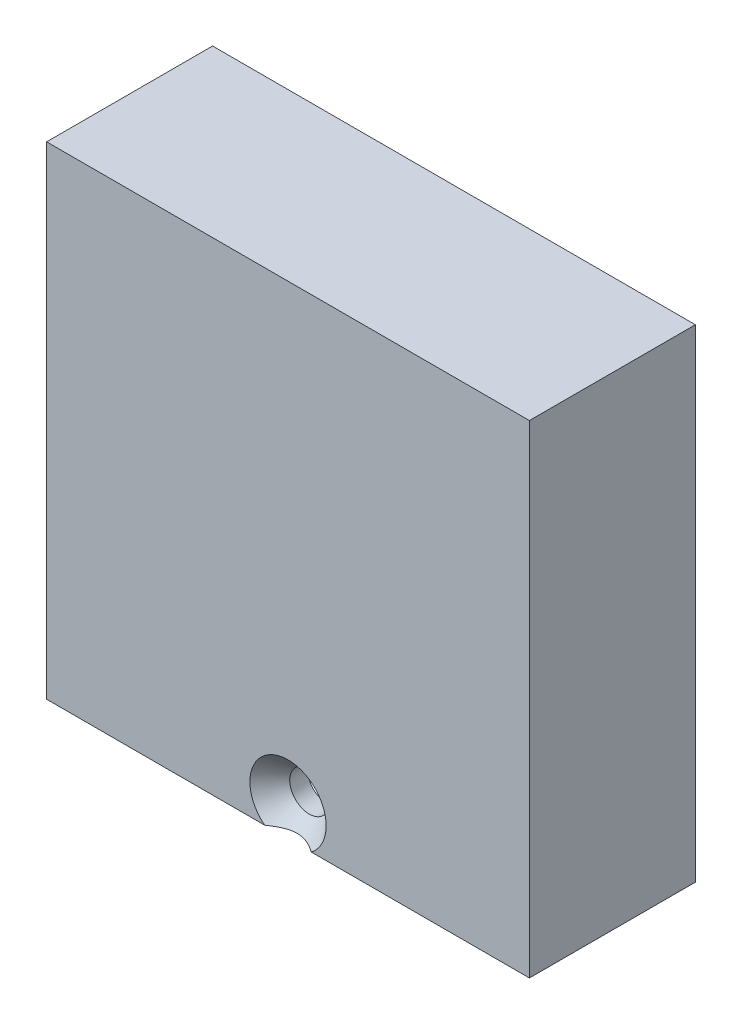
SolidWorks part; units mm, degrees
ref_plane "Plan de face" through (0, 0, 0) normal (0, 0, 1) x (1, 0, 0)
ref_plane "Plan de dessus" through (0, 0, 0) normal (0, 1, 0) x (1, 0, 0)
ref_plane "Plan de droite" through (0, 0, 0) normal (1, 0, 0) x (0, 0, -1)
sketch "Esquisse1" plane through (0, 0, 0) normal (0, 0, 1) x (1, 0, 0)
  line L1 (0, 0) -> (32, 0)
  line L2 (0, 0) -> (0, 32)
  line L3 (0, 32) -> (32, 32)
  line L4 (32, 0) -> (32, 32)
  dimension "D1" = 32
  dimension "D2" = 32
extrude "Main" add sketch "Esquisse1" along normal blind 11
sketch "Esquisse2" plane through (0, 0, 0) normal (0, -1, 0) x (1, 0, 0)
  line L0 (3.75, 0) -> (3.75, 5.2)
  line L1 (0, 0) -> (32, 0) construction
  line L2 (3.75, 5.2) -> (4.35, 5.2)
  line L3 (4.35, 5.2) -> (4.35, 6.2)
  line L4 (4.35, 6.2) -> (3.75, 6.2)
  line L5 (3.75, 6.2) -> (3.75, 8.4)
  line L6 (3.75, 8.4) -> (28.25, 8.4)
  line L7 (28.25, 8.4) -> (28.25, 6.2)
  line L8 (28.25, 6.2) -> (27.65, 6.2)
  line L9 (27.65, 6.2) -> (27.65, 5.2)
  line L10 (27.65, 5.2) -> (28.25, 5.2)
  line L11 (28.25, 5.2) -> (28.25, 0)
  line L12 (28.25, 0) -> (3.75, 0)
  line L13 (0, 11) -> (32, 11) construction
  point P13 (16, 0)
  point P15 (16, 8)
  point P18 (16, 11)
  dimension "D1" = 24.5
  dimension "D2" = 0.6
  dimension "D3" = 1
  dimension "D4" = 2.2
  dimension "D5" = 8.4
  dimension "D6" = 5.2
extrude "Main Fix" cut sketch "Esquisse2" against normal blind 28.5
sketch "Esquisse4" plane through (0, 0, 8.4) normal (0, 0, -1) x (-1, 0, 0)
  line L3 (-28.25, 28.5) -> (-28.25, 0) construction
  line L4 (-3.75, 28.5) -> (-3.75, 0) construction
  line L5 (-28.25, 15.5) -> (-28.25, 28.5)
  line L6 (-28.25, 28.5) -> (-3.75, 28.5)
  line L7 (-3.75, 28.5) -> (-3.75, 15.5)
  line L8 (-3.75, 28.5) -> (-28.25, 28.5) construction
  arc A0 (-28.25, 15.5) -> (-3.75, 15.5) centre (-16, 15.5) cw
  dimension "D1" = 12.25
  dimension "D2" = 13
extrude "Boss.-Extru.2" add sketch "Esquisse4" along normal up to surface (8.4 mm away) up to face at (16, 15.125, 0)
sketch "Esquisse5" plane through (0, 0, 5.2) normal (0, 0, -1) x (-1, 0, 0)
  line L0 (-4.35, 13.9703) -> (0, 13.9703)
  line L1 (0, 13.9703) -> (0, 32)
  line L2 (0, 32) -> (-32, 32)
  line L3 (-32, 32) -> (-32, 13.9703)
  line L4 (-32, 13.9703) -> (-27.65, 13.9703)
  line L5 (-32, 0) -> (-32, 32) construction
  line L6 (0, 32) -> (0, 0) construction
  line L7 (-32, 32) -> (0, 32) construction
  line L8 (-27.65, 19.2868) -> (-27.65, 0) construction
  arc A0 (-27.65, 13.9703) -> (-4.35, 13.9703) centre (-16, 15.5) cw
  arc A3 (-3.75, 15.5) -> (-28.25, 15.5) centre (-16, 15.5) ccw construction
  dimension "D1" = 11.75
extrude "Boss.-Extru.3" add sketch "Esquisse5" against normal up to surface (1 mm away) up to face at (27.9873, 8.7026, 6.2)
sketch "Esquisse10" plane through (0, 0, 11) normal (0, 0, 1) x (1, 0, 0)
  line L0 (0, 0) -> (32, 0) construction
  point P0 (16, 2)
  point P4 (16, 0)
  dimension "D1" = 2
hole_wizard "Fraisage pour vis à tête fraisée bombée #33" positions "Esquisse11" profile "Esquisse12" countersink size "#3" standard "Ansi Inch" end condition through all
sketch "Esquisse11" plane through (0, 0, 11) normal (0, 0, 1) x (1, 0, 0)
  point P0 (16, 2)
sketch "Esquisse12" plane through (16, 2, 11) normal (1, 0, 0) x (0, -1, 0)
  line L0 (0, 0) -> (0, 11)
  line L1 (0, 11) -> (1.3, 11)
  line L2 (1.3, 11) -> (1.3, 1.4119)
  line L3 (1.3, 1.4119) -> (2.5273, 0)
  line L5 (2.5273, 0) -> (0, 0)
  line L6 (-1.3, 1.4119) -> (-2.5273, 0) construction
  line L11 (0, -6.35) -> (0, 107.95) construction
  dimension "Diamètre du perçage jusqu'au prochain" = 2.6
  dimension "Profondeur du perçage jusqu'au prochain" = 11
  dimension "Diamètre du fraisage entrant" = 5.0546
  dimension "Angle du fraisage entrant" = 82
